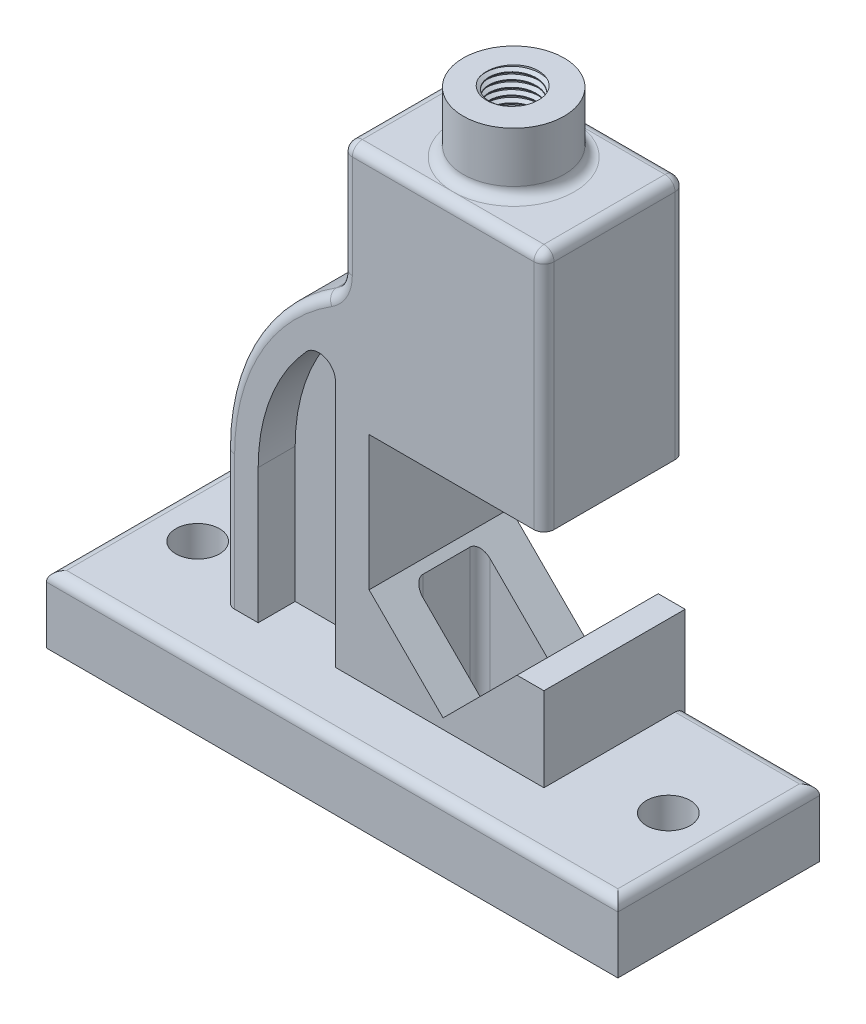
SolidWorks part; units mm, degrees
ref_plane "Front Plane" through (0, 0, 0) normal (0, 0, 1) x (1, 0, 0)
ref_plane "Top Plane" through (0, 0, 0) normal (0, 1, 0) x (1, 0, 0)
ref_plane "Right Plane" through (0, 0, 0) normal (1, 0, 0) x (0, 0, -1)
sketch "Sketch1" plane through (0, 0, 0) normal (0, 0, 1) x (1, 0, 0)
  line L0 (0, 1294) -> (0, 141.8927) construction
  line L1 (-100, 0) -> (70, 0)
  line L2 (70, 0) -> (70, 20)
  line L4 (30, 20) -> (30, 45)
  line L5 (30, 45) -> (22, 45)
  line L6 (22, 45) -> (0, 23)
  line L7 (0, 23) -> (-22, 45)
  line L8 (-22, 45) -> (-22, 85)
  line L9 (-22, 85) -> (30, 85)
  line L10 (30, 85) -> (30, 157)
  line L11 (30, 157) -> (20, 157)
  line L15 (-20, 157) -> (-30, 157)
  line L16 (-30, 157) -> (-30, 123.4429)
  line L17 (-100, 0) -> (-100, 20)
  line L19 (-65, 20) -> (-65, 60)
  line L20 (-55, 0) -> (70, 0)
  line L23 (-55, 60) -> (-55, 20)
  line L24 (-100, 20) -> (70, 20)
  line L25 (-32, 93.6303) -> (-32, 20)
  line L27 (20, 85) -> (20, 84.8607)
  line L28 (20, 84.8607) -> (-20, 84.8607)
  line L29 (-20, 84.8607) -> (-20, 85)
  line L30 (0, 85) -> (0, -46897.59) construction
  line L31 (-20, 157) -> (20, 157)
  arc A0 (-65, 60) -> (-34.6667, 114.9838) centre (0, 60) cw
  arc A1 (-40.7, 96.9934) -> (-55, 60) centre (0, 60) ccw
  arc A2 (-30, 123.4429) -> (-34.6667, 114.9838) centre (-40, 123.4429) cw
  arc A3 (-32, 93.6303) -> (-40.7, 96.9934) centre (-37, 93.6303) ccw
  point P24 (26, 45)
  point P25 (70, 10)
  point P45 (-30, 140.2214)
  dimension "D9" = 65
  dimension "D13" = 55
  dimension "D14" = 10
  dimension "D19" = 5
  dimension "D1" = 170
  dimension "D2" = 20
  dimension "D3" = 25
  dimension "D4" = 40
  dimension "D5" = 72
  dimension "D6" = 45
  dimension "D7" = 70
  dimension "D8" = 22
  dimension "D10" = 10
  dimension "D11" = 60
  dimension "D12" = 60
  dimension "D16" = 10
  dimension "D18" = 40
extrude "Boss-Extrude1" add sketch "Sketch1" along normal blind 60 contours L0 L24 L17 L1 | L24 L0 L20 L2 region at (-15, 10, 0)
extrude "Boss-Extrude2" add sketch "Sketch1<3>" along normal blind 42 contours A3 L25 L24 L4 L5 L6 L7 L8 L9 L10 L11 L31 L15 L16 A2 A0 L19 L23 A1 region at (-10.1651, 95.8083, 0)
sketch "Sketch1<3>" plane through (0, 0, 0) normal (0, 0, 1) x (1, 0, 0) same geometry as "Sketch1"
sketch "Sketch2" plane through (0, 0, 0) normal (0, -1, 0) x (1, 0, 0)
  line L0 (-100, 60) -> (70, 60) construction
  line L1 (-85, 30) -> (-78.5, 30) construction
  line L8 (48.5, 30) -> (55, 30) construction
  circle A0 centre (-85, 30) radius 6.5
  circle A1 centre (55, 30) radius 6.5
  dimension "D1" = 13
  dimension "D2" = 85
  dimension "D3" = 55
  dimension "D4" = 30
extrude "Cut-Extrude1" cut sketch "Sketch2" against normal blind 60
extrude "Boss-Extrude3" add sketch "Sketch1<6>" along normal blind 20 from offset 11 contours L25 A3 A1 L23 L24 region at (-42.7211, 55.6294, 0)
sketch "Sketch1<6>" plane through (0, 0, 0) normal (0, 0, 1) x (1, 0, 0) same geometry as "Sketch1"
sketch "Sketch3" plane through (0, 0, 0) normal (0, 0, 1) x (1, 0, 0)
  line L0 (30, 157) -> (-30, 157) construction
  line L1 (-20, 147) -> (20, 147)
  line L2 (-20, 147) -> (-20, 0)
  line L3 (-20, 0) -> (20, 0)
  line L4 (20, 147) -> (20, 0)
  line L5 (30, 85) -> (30, 157) construction
  line L6 (-100, 0) -> (70, 0) construction
  dimension "D1" = 10
  dimension "D2" = 40
  dimension "D3" = 10
extrude "Cut-Extrude2" cut sketch "Sketch3" along normal blind 20 from offset 11
sketch "Sketch4" plane through (0, 157, 0) normal (0, 1, 0) x (1, 0, 0)
  line L3 (30, -42) -> (30, 0) construction
  circle A0 centre (0, -21) radius 15
  point P9 (30, -21)
  dimension "D1" = 30
extrude "Boss-Extrude4" add sketch "Sketch4" along normal blind 18
hole_wizard "M16x2.0 Tapped Hole1" positions "Sketch5" profile "Sketch7" tap size "M16x2.0" standard "ANSI Metric" end condition up to next
sketch "Sketch5" plane through (0, 175, 0) normal (0, 1, 0) x (1, 0, 0)
  point P0 (0, -21)
sketch "Sketch7" plane through (0, 175, 21) normal (1, 0, 0) x (0, 0, 1)
  line L0 (0, 0) -> (0, 28)
  line L1 (0, 28) -> (7, 28)
  line L2 (7, 28) -> (7, 0)
  line L5 (7, 0) -> (0, 0)
  line L11 (0, -6.35) -> (0, 107.95) construction
  dimension "Thru Tap Drill Dia." = 14
  dimension "Thru Tap Drill Depth" = 28
cosmetic thread "Hole Thread1" parameters "D2"=16
fillet "Fillet1" radius 3 5 edges at (-82.5, 20, 0) (50, 20, 0) (70, 20, 30) (-100, 20, 30) (-15, 20, 60)
fillet "Fillet2" radius 3 23 edges at (-65, 38.5, 0) (-30, 140.2214, 0) (-31.244, 118.6124, 0) (-30, 140.2214, 42) (-31.244, 118.6124, 42) (-56.9137, 91.398, 42) (30, 157, 21) (0, 157, 42) (-30, 157, 21) (0, 157, 0) (-15, 157, 21) (-56.9137, 91.398, 0) (30, 121, 0) (30, 121, 42) (-65, 40, 42) (20, 116, 31) (-20, 116, 31) (20, 116, 11) (-20, 116, 11) (20, 21.5, 31) (20, 21.5, 11) (-20, 21.5, 31) (-20, 21.5, 11)
thread "Thread1" pitch 2 method cut profile "Thread Profile1" start angle 0, offset 3, length 97, pitch 2, diameter 14
ref_plane "Plane1" through (-7, 178, 21) normal (0, 0, -1) x (1, 0, 0)
sketch "Thread Profile1" plane through (-7, 178, 21) normal (0, 0, -1) x (1, 0, 0)
  line L0 (0, 0) -> (0, 2) construction
  line L11 (0, 0) -> (0, 1.75)
  line L12 (0, 1.75) -> (-1.0825, 1.125)
  line L13 (-1.0825, 1.125) -> (-1.0825, 0.625)
  line L15 (-1.0825, 0.625) -> (0, 0)
  line L17 (-1.0825, 0.875) -> (0, 0.875) construction
  point P2 (0, 0)
  dimension "Pitch" = 2
  dimension "Profile_Angle" = 60
  dimension "Profile_Land" = 0.5
  dimension "Profile_Height" = 1.0825
